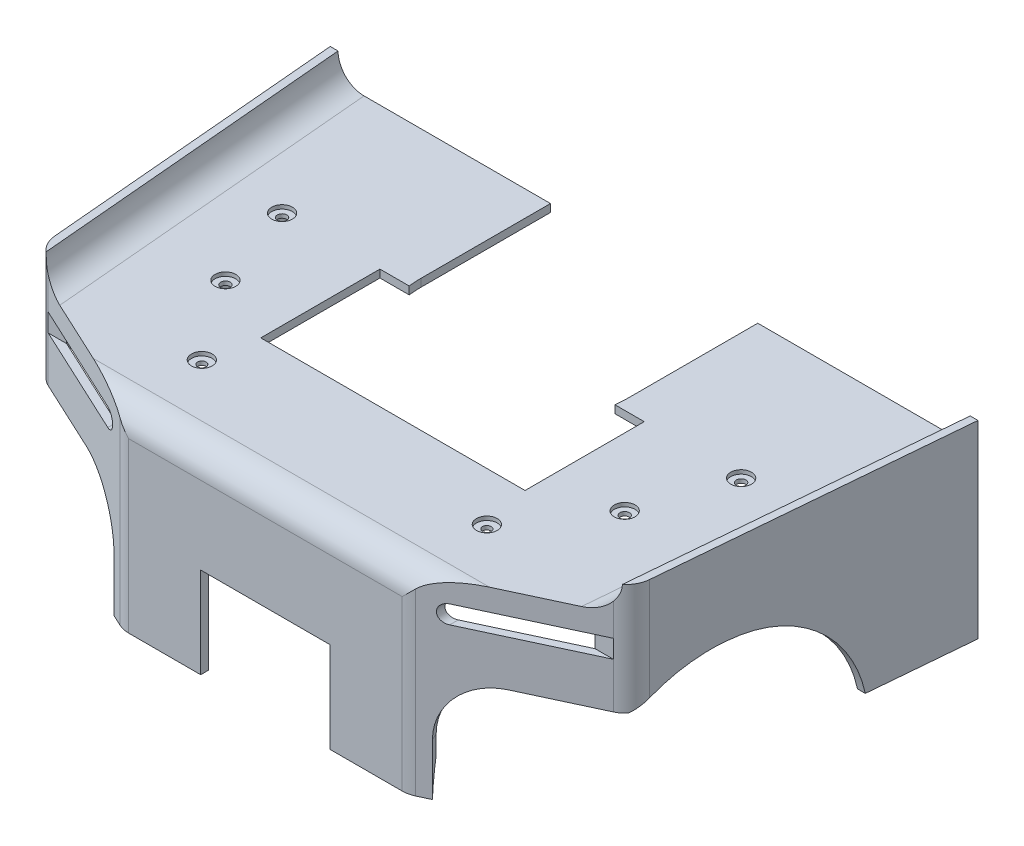
SolidWorks part; units mm, degrees
ref_plane "Alzado" through (0, 0, 0) normal (0, 0, 1) x (1, 0, 0)
ref_plane "Planta" through (0, 0, 0) normal (0, 1, 0) x (1, 0, 0)
ref_plane "Vista lateral" through (0, 0, 0) normal (1, 0, 0) x (0, 0, -1)
sketch "Croquis2" plane through (0, 0, 0) normal (1, 0, 0) x (0, 0, -1)
  line L0 (-75, -16.5) -> (-75, -68.5)
  line L1 (-75, 16.5) -> (75, 16.5)
  line L2 (-75, 16.5) -> (-75, -16.5)
  line L3 (-15, -16.5) -> (75, -16.5)
  line L4 (75, 16.5) -> (75, -16.5)
  line L5 (-75, 16.5) -> (75, -16.5) construction
  line L6 (-75, -16.5) -> (75, 16.5) construction
  line L7 (-75, -68.5) -> (-72, -68.5)
  arc A0 (-72, -68.5) -> (-15, -16.5) centre (-15, -73.7404) cw
  point P0 (0, 0)
  dimension "D6" = 33
  dimension "D1" = 150
  dimension "D2" = 33
  dimension "D3" = 52
  dimension "60" = 60
  dimension "D5" = 3
extrude "Saliente-Extruir1" add sketch "Croquis2" along normal mid plane 250
sketch "Croquis3" plane through (0, 16.5, 0) normal (0, 1, 0) x (1, 0, 0)
  line L0 (-125, 75) -> (-114.2958, -47.3499)
  line L1 (125, -75) -> (-125, -75) construction
  line L2 (-55, -75) -> (-125, -75)
  line L3 (-125, -75) -> (-125, 75)
  line L4 (0, 0) -> (0, -50000) construction
  line L8 (-114.2958, -47.3499) -> (-55, -75)
  line L10 (114.2958, -47.3499) -> (55, -75)
  line L11 (125, 75) -> (114.2958, -47.3499)
  line L12 (125, -75) -> (125, 75)
  line L13 (55, -75) -> (125, -75)
  dimension "D1" = 5
  dimension "D2" = 25
  dimension "D3" = 70
extrude "Cortar-Extruir1" cut sketch "Croquis3" against normal up to next
sketch "Croquis4" plane through (0, 16.5, 0) normal (0, 1, 0) x (1, 0, 0)
  line L5 (-111.3072, -47.0885) -> (-122.0114, 75.2615)
  line L6 (-108.8652, -75) -> (-121.9885, 75)
  line L7 (125, 75) -> (-125, 75) construction
  line L8 (122.0114, 75.2615) -> (111.3072, -47.0885)
  line L9 (121.9885, 75) -> (108.8652, -75)
  line L10 (55, -75) -> (-55, -75) construction
  line L11 (-121.9885, 75) -> (121.9885, 75)
  line L12 (-108.8652, -75) -> (108.8652, -75)
  dimension "D1" = 3
  dimension "D2" = 3
extrude "Cortar-Extruir2" cut sketch "Croquis4" against normal blind 10
shell "Vaciado1" thickness 3 removed face at (0, -35.4399, 46.5978) removed face at (0, -16.5, -30) removed face at (0, 5.75, -75) removed face at (0, -68.5, 73.5)
sketch "Croquis5" plane through (0, 6.5, 0) normal (0, 1, 0) x (1, 0, 0)
  line L0 (121.9885, 75) -> (-121.9885, 75) construction
  line L1 (-40, 25) -> (-40, 75)
  line L2 (-40, 75) -> (40, 75)
  line L3 (40, 75) -> (40, 25)
  arc A0 (-40, 25) -> (40, 25) centre (0, 25) ccw
  dimension "D1" = 80
  dimension "D2" = 50
extrude "Cortar-Extruir4" cut sketch "Croquis5" against normal blind 32
sketch "Croquis6" plane through (0, 0, 75) normal (0, 0, 1) x (1, 0, 0)
  line L0 (55, -68.5) -> (-55, -68.5) construction
  line L1 (-25, -68.5) -> (25, -68.5)
  line L2 (-25, -68.5) -> (-25, -33.5)
  line L3 (-25, -33.5) -> (25, -33.5)
  line L4 (25, -68.5) -> (25, -33.5)
  point P6 (0, -33.5)
  dimension "D1" = 50
  dimension "D2" = 35
extrude "Cortar-Extruir5" cut sketch "Croquis6" against normal blind 32
sketch "Croquis7" plane through (38.55, 0, 82.6708) normal (0.4226, 0, 0.9063) x (0.9063, 0, -0.4226)
  line L0 (25.2492, -68.5) -> (25.2492, -48.5)
  line L1 (47.2311, -26.5181) -> (83.5762, -26.5181)
  arc A0 (25.2492, -48.5) -> (47.2311, -26.5181) centre (47.2311, -48.5) cw
  ellipse E0 centre (160.1227, -73.7404) end of major axis (24.6804, -73.7404) minor radius 57.2404 (83.5762, -26.5181) -> (25.2492, -68.5) ccw construction
  ellipse E1 centre (160.1227, -73.7404) end of major axis (24.6804, -73.7404) minor radius 57.2404 (83.5762, -26.5181) -> (25.2492, -68.5) ccw
  dimension "D1" = 20
extrude "Cortar-Extruir6" cut sketch "Croquis7" against normal blind 32
mirror "Simetría1" about plane through (0, 0, 0) normal (1, 0, 0) of "Cortar-Extruir6"
fillet "Redondeo1" radius 10 10 edges at (114.2958, -5.0091, 47.3499) (-114.2958, -5.0091, 47.3499) (-54.3349, -32.5, 72) (0, 3.5, 72) (54.3349, -32.5, 72) (55, -31, 75) (-55, -31, 75) (0, 6.5, 75) (116.5724, 6.5, -13.093) (-116.5724, 6.5, -13.093)
sketch "Croquis9" plane through (0, 6.5, 0) normal (0, 1, 0) x (1, 0, 0)
  circle A0 centre (88.585, 20) radius 1.825
  circle A1 centre (77.0498, -13.41) radius 1.825
  circle A2 centre (-88.588, 20) radius 1.825
  circle A3 centre (-77.0529, -13.41) radius 1.825
  dimension "D1" = 3.65
  dimension "D2" = 3.65
  dimension "D3" = 3.65
  dimension "D4" = 3.65
extrude "Cortar-Extruir8" cut sketch "Croquis9" against normal up to next
sketch "Croquis10" plane through (0, 6.5, 0) normal (0, 1, 0) x (1, 0, 0)
  circle A0 centre (77.0498, -13.41) radius 4
  circle A1 centre (88.585, 20) radius 4
  circle A2 centre (-88.588, 20) radius 4
  circle A3 centre (-77.0529, -13.41) radius 4
  dimension "D1" = 8
  dimension "D2" = 8
  dimension "D3" = 8
  dimension "D4" = 8
extrude "Cortar-Extruir9" cut sketch "Croquis10" against normal blind 1.5
sketch "Croquis11" plane through (0, 0, 75) normal (0, 0, 1) x (1, 0, 0)
  line L0 (-69.0065, -1.9) -> (-69.0065, -8.9) construction
  line L1 (0, -33.5) -> (0, 6.5) construction
  line L2 (25, -33.5) -> (-25, -33.5) construction
  line L3 (-76.4451, 6.5) -> (76.4451, 6.5) construction
  line L4 (-69.0065, -1.9) -> (-65.9754, -1.9)
  line L7 (-65.9754, -8.9) -> (-69.0065, -8.9)
  line L8 (-125, -8.9) -> (-69.0065, -8.9)
  line L9 (-125, -16.5) -> (-125, 16.5) construction
  line L10 (-69.0065, -1.9) -> (-125, -1.9)
  line L11 (-125, -1.9) -> (-125, -8.9)
  line L12 (69.0065, -1.9) -> (65.9754, -1.9)
  line L13 (69.0065, -1.9) -> (125, -1.9)
  line L14 (125, -1.9) -> (125, -8.9)
  line L15 (125, -8.9) -> (69.0065, -8.9)
  line L16 (65.9754, -8.9) -> (69.0065, -8.9)
  arc A0 (-65.9754, -3.65) -> (-72.0376, -3.65) centre (-69.0065, -5.4) ccw construction
  arc A1 (-72.0376, -7.15) -> (-65.9754, -7.15) centre (-69.0065, -5.4) ccw construction
  arc A2 (-65.9754, -1.9) -> (-65.9754, -8.9) centre (-65.9754, -5.4) cw
  arc A3 (65.9754, -1.9) -> (65.9754, -8.9) centre (65.9754, -5.4) ccw
  dimension "D1" = 3.0311
extrude "Cortar-Extruir10" cut sketch "Croquis11" against normal up to vertex (25.2101 mm away) up to point (-109.0632, 6.5, 49.7899)
sketch "Croquis12" plane through (0, 3.5, 0) normal (0, -1, 0) x (1, 0, 0)
  line L0 (0, 75) -> (0, 22.1639) construction
  line L1 (25, 75) -> (-25, 75) construction
  circle A0 centre (55.0035, 44.555) radius 1.65
  circle A1 centre (-55.0035, 44.555) radius 1.65
  dimension "D1" = 3.3
extrude "Cortar-Extruir11" cut sketch "Croquis12" against normal up to surface (3 mm away) up to face at (-77.0529, 6.5, 17.41)
sketch "Croquis13" plane through (0, 6.5, 0) normal (0, 1, 0) x (1, 0, 0)
  line L0 (0, -15) -> (0, -75) construction
  line L1 (52.7831, -75) -> (-52.7831, -75) construction
  arc A0 (-40, 25) -> (40, 25) centre (0, 25) ccw construction
  circle A1 centre (-55.0035, -44.555) radius 4
  circle A2 centre (55.0035, -44.555) radius 4
  dimension "D1" = 8
extrude "Cortar-Extruir12" cut sketch "Croquis13" against normal blind 1.5
sketch "Croquis16" plane through (0, 6.5, 0) normal (0, 1, 0) x (1, 0, 0)
  line L0 (0, -3.3547) -> (0, -25.82) construction
  line L1 (0, -25.82) -> (133.698, -25.82) construction
  line L3 (51, -25.82) -> (-51, -25.82)
  line L4 (51, -25.82) -> (51, 20.18)
  line L5 (51, 20.18) -> (-51, 20.18)
  line L6 (-51, -25.82) -> (-51, 20.18)
  point P9 (0, -25.82)
  dimension "D1" = 102
  dimension "D2" = 46
extrude "Cortar-Extruir13" cut sketch "Croquis16" against normal through all
sketch "Croquis18" plane through (0, 6.5, 0) normal (0, 1, 0) x (1, 0, 0)
  line L0 (0, -75) -> (0, -13.1082) construction
  line L1 (52.7831, -75) -> (-52.7831, -75) construction
sketch "Croquis19" plane through (0, -16.5, 0) normal (0, -1, 0) x (-1, 0, 0)
  line L0 (-125, 75) -> (-121.9885, 75)
  line L1 (-121.9885, 75) -> (-118.489, 35)
  line L2 (-114.1146, -15) -> (-121.9885, 75) construction
  line L3 (-118.489, 35) -> (-121.5005, 35)
  line L4 (-117.126, -15) -> (-125, 75) construction
  line L5 (-121.5005, 35) -> (-125, 75)
  line L6 (-125, 75) -> (125, 75) construction
  line L7 (0, 75) -> (0, -75) construction
  line L8 (118.489, 35) -> (121.5005, 35)
  line L9 (121.9885, 75) -> (118.489, 35)
  line L10 (125, 75) -> (121.9885, 75)
  line L11 (121.5005, 35) -> (125, 75)
  dimension "D1" = 40
extrude "Saliente-Extruir2" add sketch "Croquis19" along normal blind 40
fillet "Redondeo2" radius 50 2 edges at (119.9947, -16.5, -35) (-119.9947, -16.5, -35)
